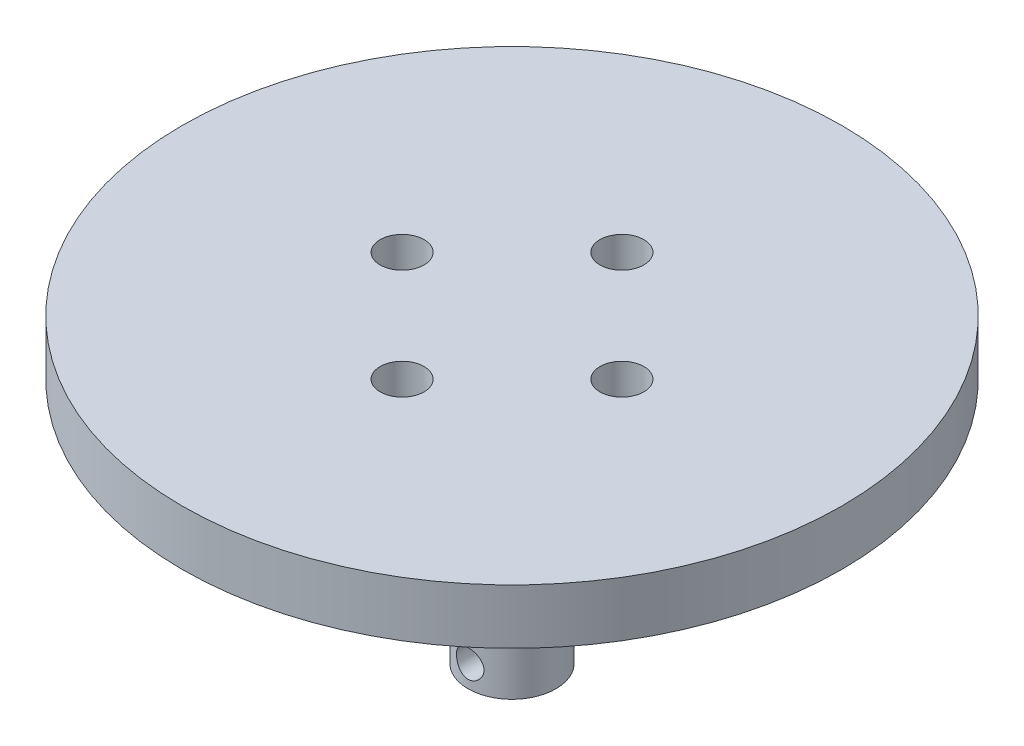
SolidWorks part; units mm, degrees
ref_plane "Front Plane" through (0, 0, 0) normal (0, 0, 1) x (1, 0, 0)
ref_plane "Top Plane" through (0, 0, 0) normal (0, 1, 0) x (1, 0, 0)
ref_plane "Right Plane" through (0, 0, 0) normal (1, 0, 0) x (0, 0, -1)
sketch "Croquis1" plane through (0, 0, 0) normal (0, 1, 0) x (1, 0, 0)
  circle A0 centre (0, 0) radius 2.05
  circle A1 centre (0, 0) radius 4
  dimension "D1" = 4.1
  dimension "D2" = 8
extrude "Saliente-Extruir1" add sketch "Croquis1" along normal blind 25.4 contours A0 | A1 A0 region at (0, 0, 0) region at (-3.8869, 0, 0)
sketch "Croquis2" plane through (0, 25.4, 0) normal (0, 1, 0) x (1, 0, 0)
  circle A1 centre (0, 0) radius 30
  dimension "D1" = 60
extrude "Saliente-Extruir2" add sketch "Croquis2" along normal blind 5 from surface starting at face at (0, 25.4, 4)
sketch "Croquis3" plane through (0, 30.4, 0) normal (0, 1, 0) x (1, 0, 0)
  circle A0 centre (0, 0) radius 10 construction
  circle A1 centre (0, 10) radius 2
  circle A2 centre (10, 0) radius 2
  circle A3 centre (0, -10) radius 2
  circle A4 centre (-10, 0) radius 2
  point P14 (0, 0)
  dimension "D1" = 20
  dimension "D2" = 4
  dimension "D5" = 20
  dimension "D4" = 10
  dimension "D3" = 4
extrude "Cortar-Extruir1" cut sketch "Croquis3" against normal blind 7.5
sketch "Croquis6" plane through (0, 0, 0) normal (0, 0, 1) x (1, 0, 0)
  circle A0 centre (0, 5) radius 1.25
  dimension "D1" = 2.5
  dimension "D2" = 5
sketch "Croquis7" plane through (0, 0, 0) normal (0, -1, 0) x (1, 0, 0)
  circle A0 centre (0, 0) radius 3.5
  dimension "D1" = 7
extrude "Cortar-Extruir3" cut sketch "Croquis7" against normal blind 3
sketch "Croquis8" plane through (0, 0, 0) normal (1, 0, 0) x (0, 0, -1)
  line L0 (-27.0724, 0) -> (-27.0724, 3)
  line L1 (-27.0724, 3) -> (35.6259, 3)
  line L2 (35.6259, 3) -> (35.6259, 0)
  line L3 (35.6259, 0) -> (-27.0724, 0)
  dimension "D1" = 3
extrude "Cortar-Extruir5" cut sketch "Croquis8" against normal mid plane 30
extrude "Cortar-Extruir6" cut sketch "Croquis1<3>" along normal blind 7.4 contours A0 region at (0, 0, 0)
sketch "Croquis1<3>" plane through (0, 0, 0) normal (0, 1, 0) x (1, 0, 0) same geometry as "Croquis1"
sketch "Croquis9" plane through (0, 3, 0) normal (0, -1, 0) x (1, 0, 0)
  line L0 (-1.2816, 1.6) -> (1.2816, 1.6)
  line L1 (0, -2.05) -> (-1.7321, -2.05) construction
  circle A0 centre (0, 0) radius 2.05 construction
  circle A1 centre (0, 0) radius 2.05
  circle M2 centre (0, 0) radius 2.05
  dimension "D2" = 4.1
  dimension "D1" = 1.6
extrude "Saliente-Extruir3" add sketch "Croquis9" against normal blind 10 contours L0 M2 region at (0, 3, 1.7818)
extrude "Cortar-Extruir7" cut sketch "Croquis6" along normal blind 10
